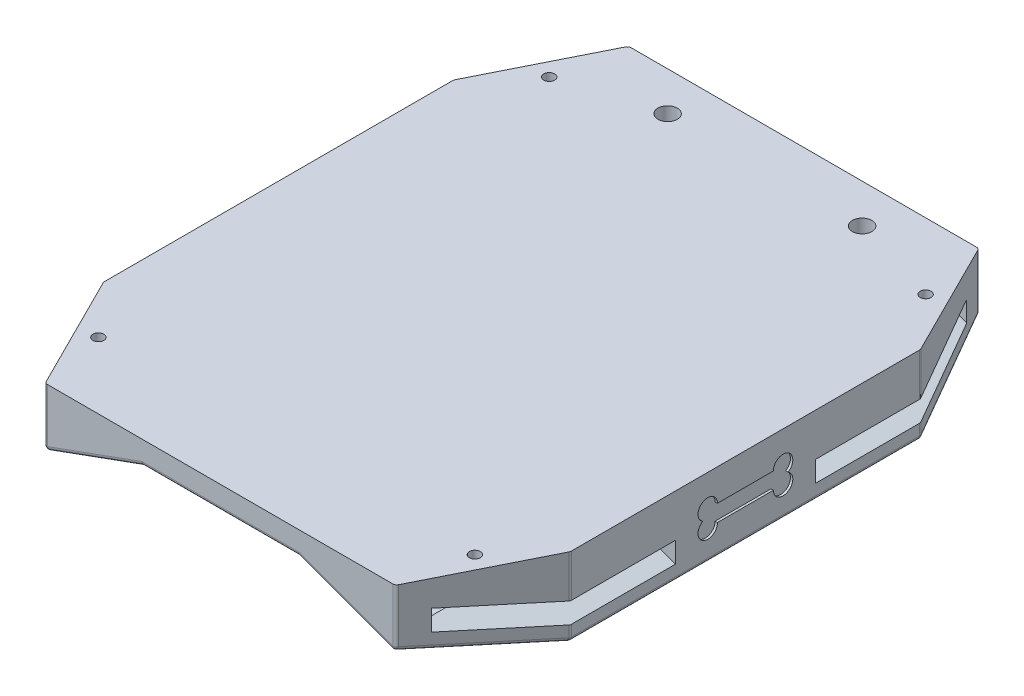
SolidWorks part; units mm, degrees
material "ABS"
ref_plane "Front Plane" through (0, 0, 0) normal (0, 0, 1) x (1, 0, 0)
ref_plane "Top Plane" through (0, 0, 0) normal (0, 1, 0) x (1, 0, 0)
ref_plane "Right Plane" through (0, 0, 0) normal (1, 0, 0) x (0, 0, -1)
sketch "Sketch1" plane through (0, 0, 0) normal (0, 1, 0) x (1, 0, 0)
  line L1 (-60, 75) -> (60, 75)
  line L2 (-60, 75) -> (-60, -75)
  line L3 (-60, -75) -> (60, -75)
  line L4 (60, 75) -> (60, -75)
  line L5 (-60, 75) -> (60, -75) construction
  line L6 (-60, -75) -> (60, 75) construction
  point P0 (0, 0)
  dimension "D1" = 120
  dimension "D2" = 150
extrude "Boss-Extrude1" add sketch "Sketch1" along normal mid plane 6
sketch "Sketch2" plane through (0, 0, 0) normal (0, 0, 1) x (1, 0, 0)
  line L0 (-60, -3) -> (-60, -17.5588)
  line L1 (-60, -17.5588) -> (-20, -3)
  line L2 (-60, -3) -> (60, -3) construction
  line L3 (-20, -3) -> (-60, -3)
  line L4 (0, 3) -> (0, -3) construction
  line L5 (-60, 3) -> (60, 3) construction
  line L6 (20, -3) -> (60, -3)
  line L7 (60, -17.5588) -> (20, -3)
  line L8 (60, -3) -> (60, -17.5588)
  dimension "D1" = 40
  dimension "D2" = 20
extrude "Boss-Extrude2" add sketch "Sketch2" along normal up to surface and the other way up to surface up to face at (0, 0, 75) other way up to face at (0, 0, -75)
sketch "Sketch3" plane through (0, 0, 0) normal (0, 0, 1) x (1, 0, 0)
  line L0 (-20, -3) -> (-46.3142, -3)
  line L1 (-46.3142, -3) -> (-60, -7.9812)
  line L2 (-60, 3) -> (-60, -17.5588) construction
  line L3 (-60, -7.9812) -> (-60, -13.3021)
  line L4 (-60, -13.3021) -> (-45.4326, -8)
  line L5 (-45.4326, -8) -> (-33.7374, -8)
  line L6 (-20, -3) -> (-60, -17.5588) construction
  line L7 (-33.7374, -8) -> (-20, -3)
  line L8 (0, 3) -> (0, -3) construction
  line L9 (-60, 3) -> (60, 3) construction
  line L10 (-20, -3) -> (20, -3) construction
  line L11 (33.7374, -8) -> (20, -3)
  line L12 (45.4326, -8) -> (33.7374, -8)
  line L13 (60, -13.3021) -> (45.4326, -8)
  line L14 (60, -7.9812) -> (60, -13.3021)
  line L15 (46.3142, -3) -> (60, -7.9812)
  line L16 (20, -3) -> (46.3142, -3)
  dimension "D1" = 5
  dimension "D2" = 5
  dimension "D3" = 4
extrude "Cut-Extrude1" cut sketch "Sketch3" along normal blind 50.8 from offset 18
mirror "Mirror1" about plane through (0, 0, 0) normal (0, 0, 1) of "Cut-Extrude1"
ref_plane "Plane1" through (0, 53, 0) normal (0, 1, 0) x (1, 0, 0)
sketch "Sketch5" plane through (0, 3, 0) normal (0, 1, 0) x (1, 0, 0)
  line L0 (-60, 0) -> (60, 0) construction
  line L1 (-60, 75) -> (-60, -75) construction
  line L2 (60, -75) -> (60, 75) construction
  line L3 (0, 75) -> (0, -75) construction
  line L4 (60, 75) -> (-60, 75) construction
  line L5 (-60, -75) -> (60, -75) construction
  line L6 (-60, -75) -> (-60, -45)
  line L7 (-60, -45) -> (-45, -75)
  line L8 (-45, -75) -> (-60, -75)
  line L9 (45, -75) -> (60, -75)
  line L10 (60, -45) -> (45, -75)
  line L11 (60, -75) -> (60, -45)
  line L12 (60, 75) -> (60, 45)
  line L13 (60, 45) -> (45, 75)
  line L14 (45, 75) -> (60, 75)
  line L15 (-45, 75) -> (-60, 75)
  line L16 (-60, 45) -> (-45, 75)
  line L17 (-60, 75) -> (-60, 45)
  dimension "D1" = 15
  dimension "D2" = 30
extrude "Cut-Extrude2" cut sketch "Sketch5" against normal through all
sketch "Sketch4" plane through (0, 53, 0) normal (0, 1, 0) x (1, 0, 0)
  line L0 (-35.7295, 60) -> (-45, 41.459)
  line L5 (-45, 41.459) -> (-45, -41.459)
  line L6 (-45, -41.459) -> (-35.7295, -60)
  line L7 (-35.7295, -60) -> (35.7295, -60)
  line L8 (35.7295, -60) -> (45, -41.459)
  line L9 (45, -41.459) -> (45, 41.459)
  line L10 (45, 41.459) -> (35.7295, 60)
  line L11 (35.7295, 60) -> (-35.7295, 60)
  line L12 (-45, 75) -> (-60, 45)
  line L13 (-60, 45) -> (-60, -45)
  line L14 (-60, -45) -> (-45, -75)
  line L15 (-45, -75) -> (45, -75)
  line L16 (45, -75) -> (60, -45)
  line L17 (60, -45) -> (60, 45)
  line L18 (60, 45) -> (45, 75)
  line L19 (45, 75) -> (-45, 75)
  line L20 (-45, 75) -> (-60, 45) construction
  line L21 (-60, 45) -> (-60, -45) construction
  line L22 (-60, -45) -> (-45, -75) construction
  line L23 (-45, -75) -> (45, -75) construction
  line L24 (45, -75) -> (60, -45) construction
  line L25 (60, -45) -> (60, 45) construction
  line L26 (60, 45) -> (45, 75) construction
  line L27 (45, 75) -> (-45, 75) construction
  dimension "D1" = 0
  dimension "D2" = 15
extrude "Boss-Extrude3" [suppressed] add sketch "Sketch4" along normal blind 4 separate body
sketch "Sketch6" plane through (0, 3, 0) normal (0, 1, 0) x (1, 0, 0)
  line L0 (-60, 0) -> (60, 0) construction
  line L1 (-60, 45) -> (-60, -45) construction
  line L2 (60, -45) -> (60, 45) construction
  line L3 (0, 75) -> (0, -75) construction
  line L4 (45, 75) -> (-45, 75) construction
  line L5 (-45, -75) -> (45, -75) construction
  line L6 (-60, -45) -> (-53.2918, -45)
  line L7 (-53.2918, -45) -> (-45, -61.5836)
  line L8 (-45, -61.5836) -> (-45, -75)
  line L9 (-45, -75) -> (-60, -45) construction
  line L10 (-45, -75) -> (-60, -45)
  line L11 (45, -75) -> (60, -45)
  line L12 (45, -61.5836) -> (45, -75)
  line L13 (53.2918, -45) -> (45, -61.5836)
  line L14 (60, -45) -> (53.2918, -45)
  line L15 (60, 45) -> (53.2918, 45)
  line L16 (53.2918, 45) -> (45, 61.5836)
  line L17 (45, 61.5836) -> (45, 75)
  line L18 (45, 75) -> (60, 45)
  line L19 (-45, 75) -> (-60, 45)
  line L20 (-45, 61.5836) -> (-45, 75)
  line L21 (-53.2918, 45) -> (-45, 61.5836)
  line L22 (-60, 45) -> (-53.2918, 45)
  dimension "D1" = 6
sketch "Sketch7" [suppressed] plane through (0, 53, 0) normal (0, -1, 0) x (-1, 0, 0)
  line L0 (35.7295, -60) -> (35.7295, -46.5836)
  line L1 (35.7295, -46.5836) -> (38.2918, -41.459)
  line L2 (38.2918, -41.459) -> (45, -41.459)
  line L3 (45, -41.459) -> (35.7295, -60)
  line L4 (60, 0) -> (-60, 0) construction
  line L5 (0, 75) -> (0, -75) construction
  line L6 (60, 0) -> (-60, 0) construction
  line L7 (0, 75) -> (0, -75) construction
  line L8 (-45, -41.459) -> (-35.7295, -60)
  line L9 (-38.2918, -41.459) -> (-45, -41.459)
  line L10 (-35.7295, -46.5836) -> (-38.2918, -41.459)
  line L11 (-35.7295, -60) -> (-35.7295, -46.5836)
  line L12 (-35.7295, 60) -> (-35.7295, 46.5836)
  line L13 (-35.7295, 46.5836) -> (-38.2918, 41.459)
  line L14 (-38.2918, 41.459) -> (-45, 41.459)
  line L15 (-45, 41.459) -> (-35.7295, 60)
  line L16 (45, 41.459) -> (35.7295, 60)
  line L17 (38.2918, 41.459) -> (45, 41.459)
  line L18 (35.7295, 46.5836) -> (38.2918, 41.459)
  line L19 (35.7295, 60) -> (35.7295, 46.5836)
  dimension "D1" = 6
loft "Loft3" [suppressed] add section "Sketch6" section "Sketch7"
mirror "Mirror2" [suppressed] about plane through (0, 0, 0) normal (1, 0, 0)
mirror "Mirror3" [suppressed] about plane through (0, 0, 0) normal (0, 0, 1)
sketch "Sketch8" plane through (0, 3, 0) normal (0, 1, 0) x (1, 0, 0)
  circle A0 centre (-48.3856, -57.9428) radius 1.6 construction
  circle A1 centre (-48.3856, -57.9428) radius 1.6 construction
  circle A2 centre (-48.3856, -57.9428) radius 1.4
  dimension "D1" = 2.8
extrude "Cut-Extrude3" cut sketch "Sketch8" against normal blind 5
mirror "Mirror4" about plane through (0, 0, 0) normal (1, 0, 0) of "Cut-Extrude3"
mirror "Mirror5" about plane through (0, 0, 0) normal (0, 0, 1) of "Mirror4"
sketch "Sketch9" plane through (60, 0, 0) normal (1, 0, 0) x (0, 0, -1)
  line L0 (0, 3) -> (0, -17.5588) construction
  line L1 (-45, 3) -> (45, 3) construction
  line L2 (-45, -17.5588) -> (45, -17.5588) construction
  line L3 (-75, -7.2794) -> (75, -7.2794) construction
  line L4 (75, -12.0993) -> (75, 3) construction
  line L5 (-7.1824, -5.1388) -> (7.1824, -5.1388)
  line L6 (-7.1824, -9.42) -> (7.1824, -9.42)
  arc A0 (-7.1824, -5.1388) -> (-10.9739, -7.2794) centre (-9.6824, -5.1388) ccw
  arc A1 (-7.1824, -9.42) -> (-10.9739, -7.2794) centre (-9.6824, -9.42) cw
  arc A2 (7.1824, -5.1388) -> (10.9739, -7.2794) centre (9.6824, -5.1388) cw
  arc A3 (7.1824, -9.42) -> (10.9739, -7.2794) centre (9.6824, -9.42) ccw
  point P11 (0, -7.2794)
  point P14 (0, -5.1388)
  point P17 (0, -9.42)
extrude "Cut-Extrude4" cut sketch "Sketch9" against normal blind 0.6
mirror "Mirror6" about plane through (0, 0, 0) normal (1, 0, 0) of "Cut-Extrude4"
fillet "Fillet1" radius 1 12 edges at (-45, -4.5496, -75) (-60, -2.4906, -45) (-60, -15.4305, -45) (-60, -15.4305, 45) (-60, -2.4906, 45) (-45, -4.5496, 75) (45, -4.5496, -75) (60, -15.4305, -45) (60, -2.4906, -45) (60, -15.4305, 45) (60, -2.4906, 45) (45, -4.5496, 75)
fillet "Fillet2" radius 1 20 edges at (-32.191, -7.4372, -75) (-44.9077, -12.0657, -74.8507) (-52.5854, -14.8601, -59.8292) (-59.9732, -17.5491, -44.9937) (-60, -17.5588, 0) (-59.9732, -17.5491, 44.9937) (-52.5854, -14.8601, 59.8292) (-44.9077, -12.0657, 74.8507) (32.191, -7.4372, -75) (44.9077, -12.0657, -74.8507) (52.5854, -14.8601, -59.8292) (59.9732, -17.5491, -44.9937) (60, -17.5588, 0) (59.9732, -17.5491, 44.9937) (52.5854, -14.8601, 59.8292) (44.9077, -12.0657, 74.8507) (0, -3, -75) (0, -3, 75) (-32.191, -7.4372, 75) (32.191, -7.4372, 75)
sketch "Sketch10" plane through (0, 3, 0) normal (0, 1, 0) x (1, 0, 0)
  line L0 (-60, 65) -> (60, 65) construction
  line L1 (-60, 44.7639) -> (-60, -44.7639) construction
  line L2 (60, -44.7639) -> (60, 44.7639) construction
  line L3 (0, 75) -> (0, -75) construction
  line L4 (44.382, 75) -> (-44.382, 75) construction
  line L5 (-44.382, -75) -> (44.382, -75) construction
  circle A0 centre (-25, 65) radius 2.5
  circle A1 centre (25, 65) radius 2.5
  dimension "D1" = 5
  dimension "D2" = 10
  dimension "D3" = 50
extrude "Cut-Extrude5" cut sketch "Sketch10" against normal through all
